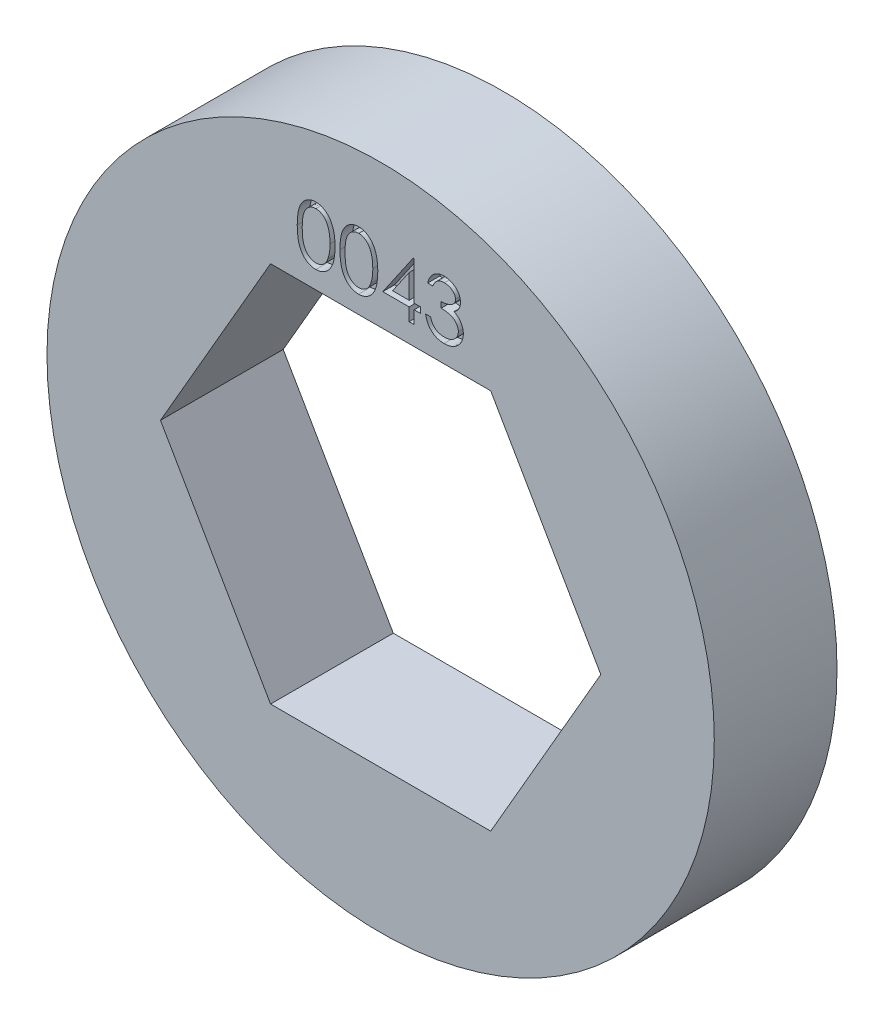
SolidWorks part; units mm, degrees
material "Nylon 101"
ref_plane "Front Plane" through (0, 0, 0) normal (0, 0, 1) x (1, 0, 0)
ref_plane "Top Plane" through (0, 0, 0) normal (0, 1, 0) x (1, 0, 0)
ref_plane "Right Plane" through (0, 0, 0) normal (1, 0, 0) x (0, 0, -1)
sketch "Sketch1" plane through (0, 0, 0) normal (0, 0, 1) x (1, 0, 0)
  line L1 (3.6662, 6.35) -> (-3.6662, 6.35)
  line L2 (-3.6662, 6.35) -> (-7.3323, 0)
  line L3 (-7.3323, 0) -> (-3.6662, -6.35)
  line L4 (-3.6662, -6.35) -> (3.6662, -6.35)
  line L5 (3.6662, -6.35) -> (7.3323, 0)
  line L6 (7.3323, 0) -> (3.6662, 6.35)
  circle A1 centre (0, 0) radius 11.1125
  circle A2 centre (0, 0) radius 6.35 construction
  dimension "D1" = 22.225
  dimension ".5" = 12.7
extrude "Boss-Extrude1" add sketch "Sketch1" along normal blind 4.0876
sketch "Sketch2" plane through (0, 0, 4.0876) normal (0, 0, 1) x (1, 0, 0)
  line L0 (-3.6662, 6.985) -> (3.6662, 6.985) construction
  line L1 (3.6662, 6.35) -> (-3.6662, 6.35) construction
  text T0 "0043" font "Century Gothic" height in points 7
  point P2 (0, 0)
  point P4 (0, 0)
  dimension "D1" = 0.635
extrude "Cut-Extrude1" cut sketch "Sketch2" against normal blind 0.4
